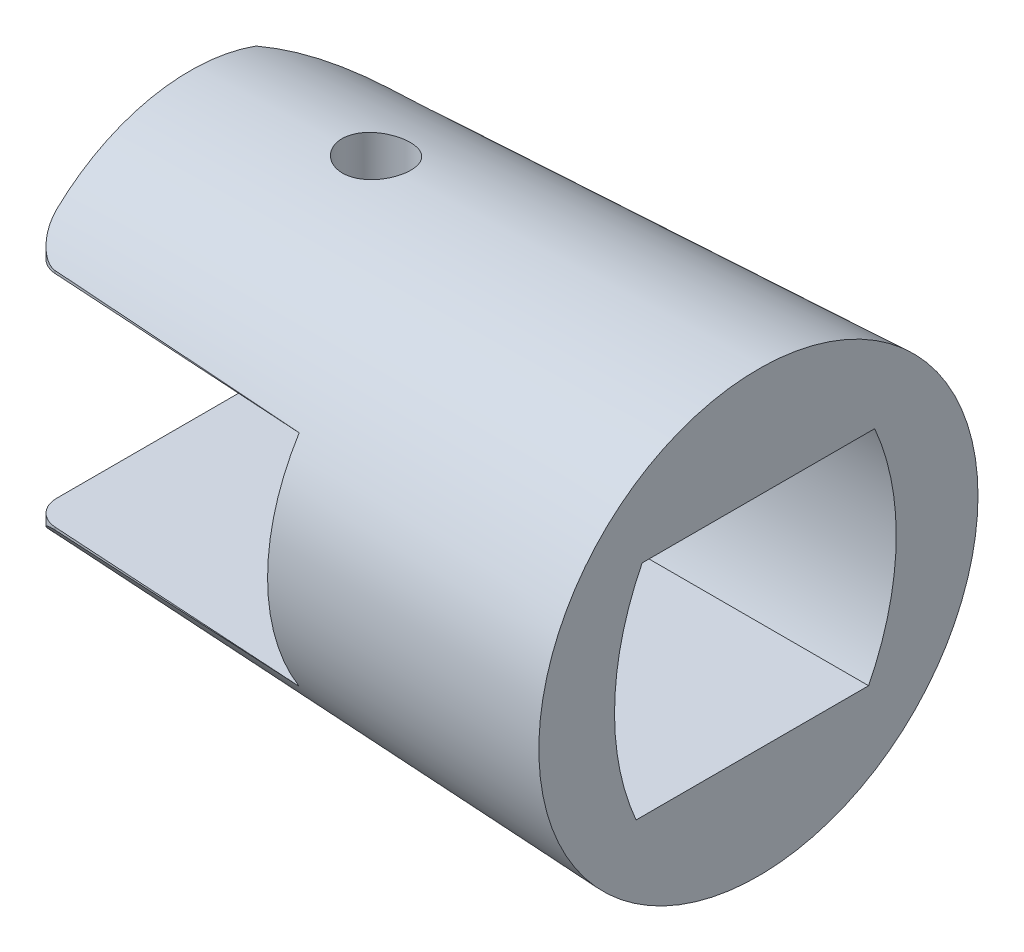
SolidWorks part; units mm, degrees
ref_plane "Front plane" through (0, 0, 0) normal (0, 0, 1) x (1, 0, 0)
ref_plane "Base plane" through (0, 0, 0) normal (0, 1, 0) x (1, 0, 0)
ref_plane "Right plane" through (0, 0, 0) normal (1, 0, 0) x (0, 0, -1)
sketch "Sketch1" plane through (0, 0, 0) normal (1, 0, 0) x (0, 0, -1)
  circle A0 centre (0, 0) radius 8.5
  dimension "D1" = 17
sketch "Sketch3" plane through (0, 0, 0) normal (0, 1, 0) x (1, 0, 0)
  line L0 (0, 0) -> (-22, 0)
  dimension "D1" = 22
ref_plane "Plane1" through (-22, 0, 0) normal (1, 0, 0) x (0, 0, -1)
sketch "Sketch2" plane through (-22, 0, 0) normal (1, 0, 0) x (0, 0, -1)
  circle A0 centre (0, 0) radius 7.5
loft "Loft1" add profiles "Sketch2", "Sketch1" connector at (-22, 1.76, -7.2906) connector at (0, 2.119, -8.2316)
sketch "Sketch4" plane through (0, 0, 0) normal (0, 0, 1) x (1, 0, 0)
  line L0 (0, 0) -> (-10, 0) construction
  line L1 (0, 0) -> (-22, 0) construction
  line L2 (-11, 4.25) -> (-24.9848, 4.25)
  line L3 (-11, 4.25) -> (-11, -4.25)
  line L4 (-24.9848, 4.25) -> (-24.9848, -4.25)
  line L5 (-24.9848, -4.25) -> (-11, -4.25)
  line L6 (-11, -4.25) -> (-10.9931, -4.2764)
  line L7 (0, -8.5) -> (0, 8.5) construction
  dimension "D1" = 10
  dimension "D2" = 8.5
  dimension "D3" = 4.25
  dimension "D4" = 11
extrude "Cut-Extrude1" cut sketch "Sketch4" against normal blind 10 and the other way blind 10 contours L4 L5 L3 L2 region at (-17.9924, 0, 0)
sketch "Sketch5" plane through (0, 0, 0) normal (0, 1, 0) x (1, 0, 0)
  line L0 (-11, 6.7777) -> (-11, -6.7777)
  line L1 (-11, -6.7777) -> (-23.0023, -6.0429)
  line L2 (-23.0023, -6.0429) -> (-23.0231, -1.4883)
  line L3 (-11, 6.7777) -> (-16.5274, 6.6846)
  line L4 (-11, -6.7777) -> (-11, -8) construction
  line L5 (-11, 6.7777) -> (-11, 10.3705)
  line L6 (-11, 10.3705) -> (-27.9181, 10.3705)
  line L7 (-27.9181, 10.3705) -> (-27.9181, -8.5015)
  line L8 (-27.9181, -8.5015) -> (-11, -8.5015)
  line L9 (-11, -8.5015) -> (-11, -6.7777)
  arc A0 (-16.5274, 6.6846) -> (-23.0231, -1.4883) centre (-14.6815, -1.4502) ccw
  spline S0 degree 3 poles (-11, -6.7777) (-14.6668, -6.581) (-18.3335, -6.3819) (-22, -6.1796) knots 0 0 0 0 1 1 1 1 construction
  spline S1 degree 3 poles (-22, 6.1796) (-18.3335, 6.3819) (-14.6668, 6.581) (-11, 6.7777) knots 0 0 0 0 1 1 1 1 construction
  dimension "D4" = 5.5274
  dimension "D6" = 8.3417
  dimension "D1" = 12.0023
  dimension "D2" = 4.5546
  dimension "D3" = 86.496
  dimension "D5" = 89.035
extrude "Cut-Extrude2" cut sketch "Sketch5" against normal blind 10 and the other way blind 10 contours A0 L3 L5 L6 L7 L8 L9 L1 L2 region at (-13.768, 0, -6.9846)
sketch "Sketch6" plane through (0, 0, 0) normal (0, 1, 0) x (1, 0, 0)
  line L0 (-11, -8) -> (-15.3, -8) construction
  line L1 (-15.3, -8) -> (-15.3, 0.5) construction
  circle A0 centre (-15.3, 0.5) radius 1.25
  dimension "D1" = 4.3
  dimension "D2" = 8.5
extrude "Cut-Extrude3" cut sketch "Sketch6" against normal blind 10 and the other way blind 10
sketch "Sketch7" plane through (0, 0, 0) normal (1, 0, 0) x (0, 0, -1)
  line L0 (5.1446, 4.1876) -> (5.1446, -4.2327)
  line L2 (-3.4805, 4.1876) -> (-3.4805, -4.3677)
  arc A0 (5.1446, 4.1876) -> (-3.4805, 4.1876) centre (0.8321, -5.3223) ccw
  arc A1 (5.1446, -4.2327) -> (-3.4805, -4.3677) centre (0.7011, 4.0719) cw
sketch "Sketch8" plane through (0, 0, 0) normal (1, 0, 0) x (0, 0, -1)
  line L0 (-4.5, 4.25) -> (4.5, 4.25)
  line L1 (-4.7349, -4.25) -> (4.2651, -4.25)
  line L2 (-8.5, 0) -> (8.5, 0) construction
  line L3 (0, -8.5) -> (0, 8.5) construction
  line L4 (0, 8.5) -> (0, 5.4132) construction
  arc A0 (-4.5, 4.25) -> (-4.7349, -4.25) centre (4.4303, -0.25) ccw
  arc A1 (4.5, 4.25) -> (4.2651, -4.25) centre (-4.6652, 0.25) cw
  circle A2 centre (0, 0) radius 8.5 construction
  dimension "D1" = 10
  dimension "D2" = 9
  dimension "D3" = 4.5
  dimension "D4" = 8.5
  dimension "D5" = 4.25
extrude "Cut-Extrude4" cut sketch "Sketch8" against normal blind 12
fillet "Fillet1" radius 1 2 edges
